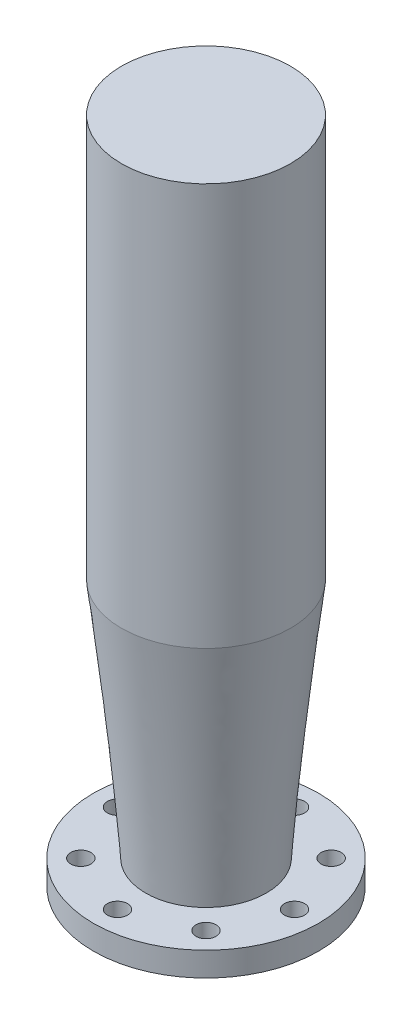
SolidWorks part; units mm, degrees
ref_plane "Plano frontal" through (0, 0, 0) normal (0, 0, 1) x (1, 0, 0)
ref_plane "Plano superior" through (0, 0, 0) normal (0, 1, 0) x (1, 0, 0)
ref_plane "Plano direito" through (0, 0, 0) normal (1, 0, 0) x (0, 0, -1)
sketch "Esboço1" plane through (0, 0, 0) normal (0, 1, 0) x (1, 0, 0)
  circle A0 centre (0, 0) radius 14
  circle A1 centre (0, 11) radius 1.25
  circle A2 centre (7.7782, 7.7782) radius 1.25
  circle A3 centre (11, 0) radius 1.25
  circle A4 centre (7.7782, -7.7782) radius 1.25
  circle A5 centre (0, -11) radius 1.25
  circle A6 centre (-7.7782, -7.7782) radius 1.25
  circle A7 centre (-11, 0) radius 1.25
  circle A8 centre (-7.7782, 7.7782) radius 1.25
  point P22 (0, 0)
  dimension "D1" = 28
  dimension "D3" = 2.5
  dimension "D2" = 11
  dimension "D5" = 11
  dimension "D4" = 8
extrude "Ressalto-extrusão1" add sketch "Esboço1" along normal blind 3
sketch "Esboço2" plane through (0, 3, 0) normal (0, 1, 0) x (1, 0, 0)
  circle A0 centre (0, 0) radius 7.5
  dimension "D1" = 15
ref_plane "Plano1" through (0, 33, 0) normal (0, 1, 0) x (1, 0, 0)
sketch "Esboço3" plane through (0, 33, 0) normal (0, 1, 0) x (1, 0, 0)
  circle A0 centre (0, 0) radius 10.5
  dimension "D1" = 21
loft "Loft1" add profiles "Esboço2", "Esboço3" connector at (-7.1559, 3, 2.2458) connector at (-10.4307, 33, -1.2047)
sketch "Esboço4" plane through (0, 33, 0) normal (0, 1, 0) x (1, 0, 0)
  circle A0 centre (0, 0) radius 10.5
  dimension "D1" = 21
extrude "Ressalto-extrusão3" add sketch "Esboço4" along normal blind 50
